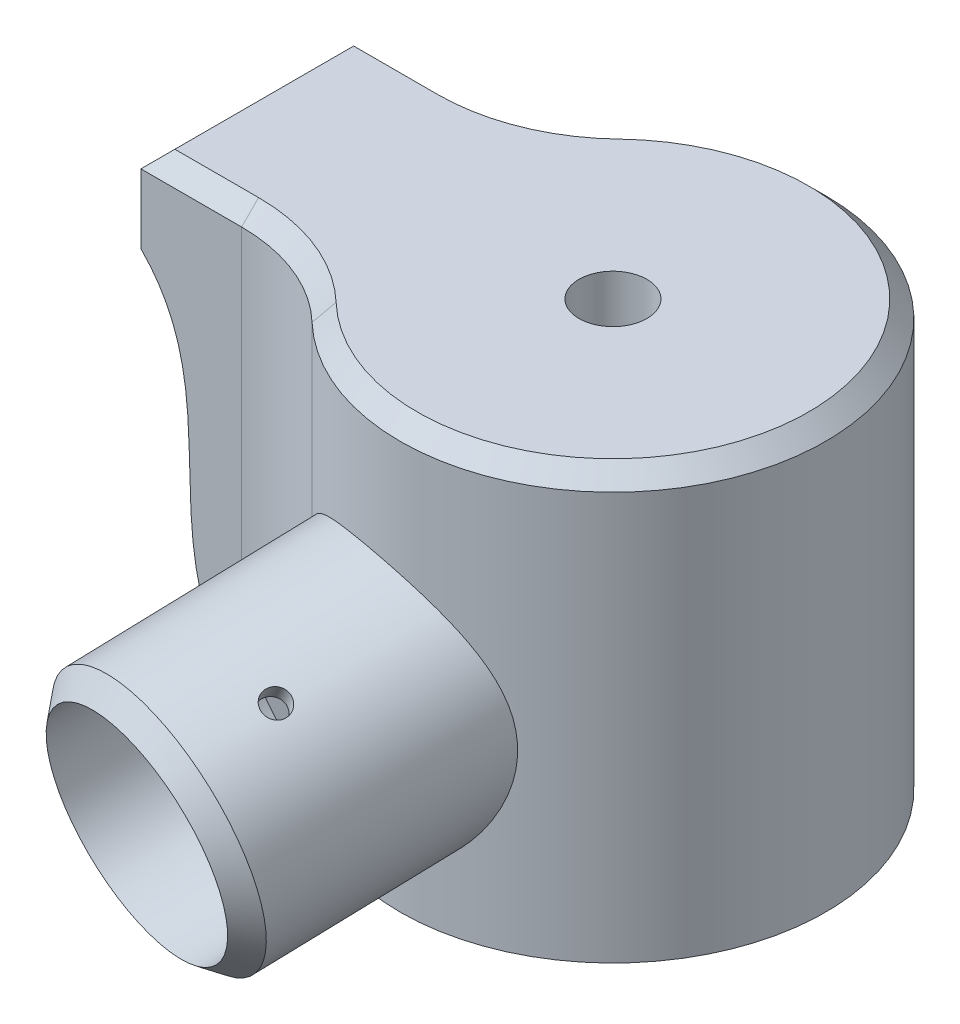
SolidWorks part; units mm, degrees
material "Melamine resin"
ref_plane "Front Plane" through (0, 0, 0) normal (0, 0, 1) x (1, 0, 0)
ref_plane "Top Plane" through (0, 0, 0) normal (0, 1, 0) x (1, 0, 0)
ref_plane "Right Plane" through (0, 0, 0) normal (1, 0, 0) x (0, 0, -1)
sketch "Sketch1" plane through (0, 0, 0) normal (0, 1, 0) x (1, 0, 0)
  line L3 (-34.0477, -12.5248) -> (-22.1886, -12.5248)
  line L4 (-34.0477, -12.5248) -> (-34.0477, 12.5248)
  line L5 (-34.0477, 12.5248) -> (-22.1886, 12.5248)
  arc A3 (-8.3278, -18.0914) -> (-22.1886, -12.5248) centre (-22.1886, -32.5646) ccw
  arc A4 (-22.1886, 12.5248) -> (-8.3278, 18.0914) centre (-22.1886, 32.5646) ccw
  arc A5 (-8.3278, -18.0914) -> (-8.3278, 18.0914) centre (8.9981, 0) ccw
  dimension "D1" = 20.0397
  dimension "D2" = 25.0497
extrude "Boss-Extrude2" add sketch "Sketch1" along normal blind 50
ref_axis "Axis1" through (8.9981, 50, 0) along (0, -1, 0)
ref_point "Point1"
ref_plane "Plane1" through (0, 25, 0) normal (0, 1, 0) x (1, 0, 0)
sketch "Sketch2" plane through (0, 25, 0) normal (0, 1, 0) x (1, 0, 0)
  point P0 (8.9981, 0)
chamfer "Chamfer1" distance 2 angle 45 5 edges at (-14.7202, 50, 13.9685) (-14.7202, 50, -13.9685) (34.0477, 50, 0) (-28.1181, 50, 12.5248) (-28.1181, 50, -12.5248)
sketch3d "3DSketch1"
  line L0 (8.9981, 25, 0) -> (-7.5398, 5.3755, 91.6321)
  line L2 (8.9981, 50, 0) -> (8.9981, 0, 0) construction
  line L4 (-23.4294, -13.4798, 179.6725) -> (8.9981, 25, 0) construction
ref_plane "Plane2" through (8.9981, 25, 0) normal (-0.1738, -0.2062, 0.9629) x (0.9848, -0.0373, 0.1698)
sketch "Sketch3" plane through (8.9981, 25, 0) normal (-0.1738, -0.2062, 0.9629) x (0.9848, -0.0373, 0.1698)
  circle A0 centre (0, 0) radius 15
  dimension "D1" = 30
extrude "Boss-Extrude3" add sketch "Sketch3" along a picked direction on the side of the normal blind 50
sketch "Sketch5" plane through (-7.5218, -8.9257, 41.6767) normal (-0.1738, -0.2062, 0.9629) x (0.9848, -0.0373, 0.1698)
  circle A0 centre (7.9298, 24.4526) radius 12.7
  dimension "D1" = 25.4
extrude "Cut-Extrude1" cut sketch "Sketch5" against normal blind 21
chamfer "Chamfer2" distance 3 angle 45 1 edges at (0.3084, 0.0211, 45.006)
ref_plane "Plane3" through (-22.1886, 48, -12.5248) normal (-0.5004, -0.8237, -0.2667) x (-0.8658, 0.4737, 0.1612)
sketch "Sketch6" plane through (-22.1886, 48, -12.5248) normal (-0.5004, -0.8237, -0.2667) x (-0.8658, 0.4737, 0.1612)
  line L0 (-23.778, -63.2237) -> (-27.9772, -56.4144) construction
  line L2 (-35.8773, -19.269) -> (-16.0818, -112.3453) construction
  circle A0 centre (-27.9772, -56.4144) radius 1.5
  dimension "D1" = 3
  dimension "D2" = 8
extrude "Cut-Extrude2" cut sketch "Sketch6" against normal mid plane 97
ref_point "Point2"
sketch "Sketch7" plane through (0, 0, 0) normal (0, -1, 0) x (-1, 0, 0)
  circle A0 centre (-8.9981, 0) radius 4
  dimension "D1" = 8
extrude "Cut-Extrude3" cut sketch "Sketch7" against normal blind 82
sketch "Sketch9" plane through (0, 0, 0) normal (0, -1, 0) x (1, 0, 0)
  circle A0 centre (8.9981, 0) radius 11
  dimension "D1" = 22
extrude "Cut-Extrude4" cut sketch "Sketch9" against normal blind 8
chamfer "Chamfer3" distance 2 angle 45 1 edges at (-34.0477, 50, 0)
sketch "Sketch10" plane through (0, 0, -12.5248) normal (0, 0, -1) x (-1, 0, 0)
  line L0 (22.1867, 0) -> (34.0477, 0)
  line L1 (34.0477, 0) -> (34.0477, 39.8592)
  line L2 (34.0477, 48) -> (34.0477, 0) construction
  line L3 (34.0477, 48) -> (22.1886, 48) construction
  spline S0 degree 3 poles (22.1867, 0) (33.5541, 11.2638) (23.1647, 28.9343) (34.0477, 39.8592) knots 0 0 0 0 1 1 1 1
extrude "Cut-Extrude5" cut sketch "Sketch10" against normal blind 96
sketch3d "3DSketch2"
  line L0 (8.9981, 50, 0) -> (8.9981, 0, 0) construction
  point P0 (8.9981, 25, 0)
